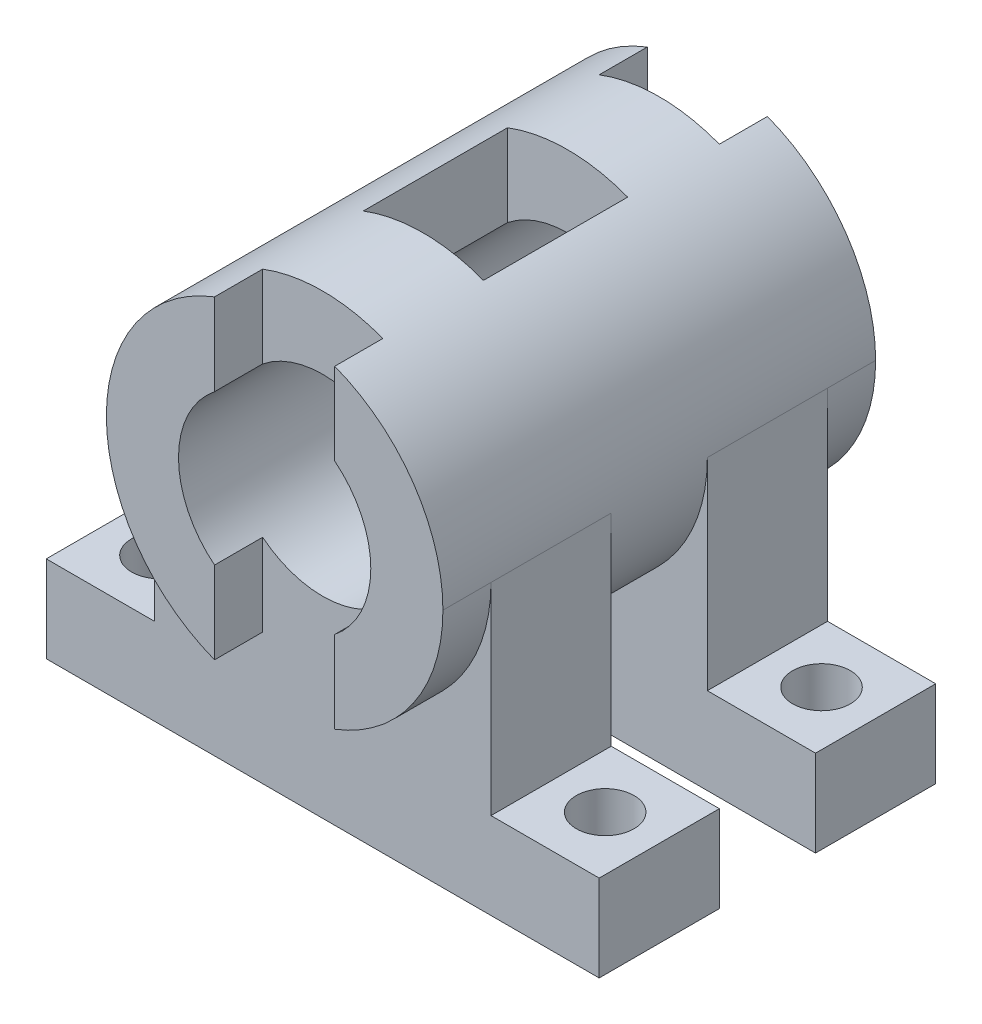
SolidWorks part; units mm, degrees
ref_plane "Front Plane" through (0, 0, 0) normal (0, 0, 1) x (1, 0, 0)
ref_plane "Top Plane" through (0, 0, 0) normal (0, 1, 0) x (1, 0, 0)
ref_plane "Right Plane" through (0, 0, 0) normal (1, 0, 0) x (0, 0, -1)
sketch "Sketch1" plane through (0, 0, 0) normal (0, 0, 1) x (1, 0, 0)
  line L0 (-57.5, 0) -> (57.5, 0)
  line L1 (57.5, 0) -> (57.5, 18)
  line L2 (57.5, 18) -> (35, 18)
  line L3 (35, 18) -> (35, 60)
  line L4 (35, 60) -> (-35, 60)
  line L5 (0, 60) -> (0, 0) construction
  line L6 (-35, 18) -> (-35, 60)
  line L7 (-57.5, 18) -> (-35, 18)
  line L8 (-57.5, 0) -> (-57.5, 18)
  line L9 (-12.5, 4.9966) -> (-12.5, 115.0034)
  line L10 (-12.5, 4.9966) -> (12.5, 4.9966)
  line L11 (-12.5, 115.0034) -> (12.5, 115.0034)
  line L12 (12.5, 4.9966) -> (12.5, 115.0034)
  line L13 (-12.5, 4.9966) -> (12.5, 115.0034) construction
  line L14 (-12.5, 115.0034) -> (12.5, 4.9966) construction
  circle A2 centre (0, 60) radius 35
  circle A3 centre (0, 60) radius 20
  dimension "D5" = 40
  dimension "D1" = 115
  dimension "D2" = 18
  dimension "D3" = 60
  dimension "D4" = 70
  dimension "D6" = 25
extrude "Boss-Extrude1" add sketch "Sketch1" along normal blind 10 and the other way blind 80 contours A3 L9 A2 L4 | A3 L12 A2 L9 | A3 L4 A2 L12 | A3 L12 A2 L4 | A3 L9 A2 L12 | A3 L4 A2 L9 region at (-22.9323, 74.2942, 0) region at (-22.9323, 45.7058, 0) region at (22.9323, 45.7058, 0) region at (22.9323, 74.2942, 0) region at (0, 86.387, 0) region at (0, 33.613, 0)
extrude "Boss-Extrude2" add sketch "Sketch1<5>" against normal blind 25 contours A2 L6 L7 L8 L0 L1 L2 L3 L12 L10 L9 | A2 L9 L10 L12 region at (-56.2029, 9, 0) region at (0, 15.3891, 0)
sketch "Sketch1<5>" plane through (0, 0, 0) normal (0, 0, 1) x (1, 0, 0) same geometry as "Sketch1"
extrude "Cut-Extrude1" cut sketch "Sketch1<6>" along normal through all contours L12 L11 L9 L10
sketch "Sketch1<6>" plane through (0, 0, 0) normal (0, 0, 1) x (1, 0, 0) same geometry as "Sketch1"
ref_plane "Plane1" through (0, 0, -35) normal (0, 0, 1) x (1, 0, 0)
mirror "Mirror1" about plane through (0, 0, -35) normal (0, 0, 1) of "Cut-Extrude1", "Boss-Extrude2"
sketch "Sketch2" plane through (0, 18, 0) normal (0, 1, 0) x (1, 0, 0)
  line L0 (-57.5, 25) -> (-35, 25) construction
  line L1 (-35, 35) -> (35, 35) construction
  line L2 (-35, 45) -> (-35, 25) construction
  line L3 (35, 25) -> (35, 45) construction
  line L4 (0, 0) -> (0, 59.1672) construction
  circle A0 centre (-46.25, 12.5) radius 6
  circle A1 centre (-46.25, 57.5) radius 6
  circle A2 centre (46.25, 12.5) radius 6
  circle A3 centre (46.25, 57.5) radius 6
  point P4 (-46.25, 25)
  dimension "D2" = 12
  dimension "D1" = 45
extrude "Cut-Extrude2" cut sketch "Sketch2" against normal through all
ref_plane "Plane2" through (0, 60, 0) normal (0, -1, 0) x (-1, 0, 0)
sketch "Sketch3" plane through (0, 60, 0) normal (0, -1, 0) x (-1, 0, 0)
  line L0 (0, 0) -> (0, 71.8518) construction
  line L5 (12.5, 50.9259) -> (12.5, 20.9259)
  line L6 (12.5, 50.9259) -> (-12.5, 50.9259)
  line L7 (12.5, 20.9259) -> (-12.5, 20.9259)
  line L8 (-12.5, 50.9259) -> (-12.5, 20.9259)
  line L9 (12.5, 50.9259) -> (-12.5, 20.9259) construction
  line L10 (12.5, 20.9259) -> (-12.5, 50.9259) construction
  point P0 (0, 35.9259)
  point P1 (0, 35.9259)
  dimension "D1" = 25
  dimension "D2" = 30
extrude "Cut-Extrude3" cut sketch "Sketch3" against normal through all
